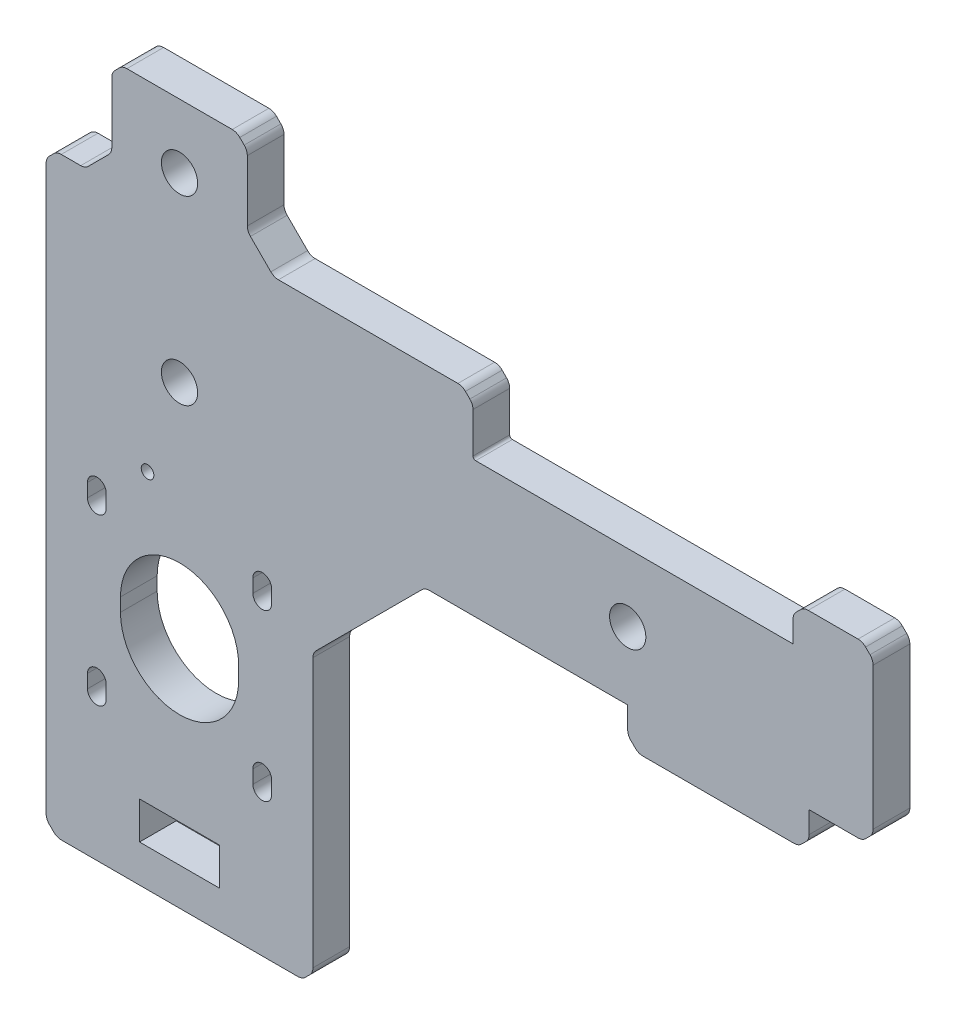
SolidWorks part; units mm, degrees
ref_plane "Front Plane" through (0, 0, 0) normal (0, 0, 1) x (1, 0, 0)
ref_plane "Top Plane" through (0, 0, 0) normal (0, 1, 0) x (1, 0, 0)
ref_plane "Right Plane" through (0, 0, 0) normal (1, 0, 0) x (0, 0, -1)
sketch "Sketch1" plane through (0, 0, 0) normal (0, 0, 1) x (1, 0, 0)
  line L1 (25, -65.675) -> (-25, -65.675)
  line L2 (25, -65.675) -> (25, 65.675)
  line L3 (25, 65.675) -> (-25, 65.675)
  line L4 (-25, -65.675) -> (-25, 65.675)
  line L5 (25, -65.675) -> (-25, 65.675) construction
  line L6 (25, 65.675) -> (-25, -65.675) construction
  point P0 (0, 0)
  dimension "D1" = 50
  dimension "D2" = 131.35
extrude "Boss-Extrude1" add sketch "Sketch1" along normal blind 6.88
sketch "Sketch2" plane through (0, 0, 6.88) normal (0, 0, 1) x (1, 0, 0)
  line L1 (15.5, -36.175) -> (-15.5, -36.175) construction
  line L2 (15.5, -36.175) -> (15.5, -5.175) construction
  line L3 (15.5, -5.175) -> (-15.5, -5.175) construction
  line L4 (-15.5, -36.175) -> (-15.5, -5.175) construction
  line L5 (15.5, -36.175) -> (-15.5, -5.175) construction
  line L6 (15.5, -5.175) -> (-15.5, -36.175) construction
  line L7 (-25, -65.675) -> (25, -65.675) construction
  line L8 (25, 65.675) -> (-25, 65.675) construction
  circle A0 centre (0, -20.675) radius 11.075
  circle A1 centre (-15.5, -5.175) radius 1.75
  circle A2 centre (-15.5, -36.175) radius 1.75
  circle A3 centre (15.5, -36.175) radius 1.75
  circle A4 centre (15.5, -5.175) radius 1.75
  circle A5 centre (0, 53.675) radius 3.4
  circle A6 centre (0, 19.675) radius 3.4
  dimension "D3" = 3.5
  dimension "D4" = 22.15
  dimension "D7" = 6.8
  dimension "D1" = 31
  dimension "D2" = 45
  dimension "D5" = 34
  dimension "D6" = 12
extrude "Cut-Extrude1" cut sketch "Sketch2" against normal through all
sketch "Sketch3" plane through (0, 0, 6.88) normal (0, 0, 1) x (1, 0, 0)
  line L0 (-25, -65.675) -> (25, -65.675) construction
  line L1 (7.5, -51.675) -> (-7.5, -51.675)
  line L2 (7.5, -51.675) -> (7.5, -58.675)
  line L3 (7.5, -58.675) -> (-7.5, -58.675)
  line L4 (-7.5, -51.675) -> (-7.5, -58.675)
  line L5 (7.5, -51.675) -> (-7.5, -58.675) construction
  line L6 (7.5, -58.675) -> (-7.5, -51.675) construction
  point P0 (0, -55.175)
  dimension "D1" = 15
  dimension "D2" = 7
  dimension "D3" = 7
extrude "Cut-Extrude2" cut sketch "Sketch3" against normal blind 6.88
sketch "Sketch4" plane through (0, 0, 6.88) normal (0, 0, 1) x (1, 0, 0)
  line L0 (25, 9.325) -> (130, 9.325)
  line L1 (25, -65.675) -> (25, 65.675) construction
  line L2 (130, 9.325) -> (130, 34.725)
  line L3 (130, 34.725) -> (25, 34.725)
  line L4 (25, 34.725) -> (25, 9.325)
  line L5 (-25, 65.675) -> (-25, -65.675) construction
  line L6 (130, 22.025) -> (0, 22.025) construction
  line L7 (-25, -65.675) -> (25, -65.675) construction
  dimension "D1" = 25.4
  dimension "D2" = 155
  dimension "D3" = 75
extrude "Boss-Extrude2" add sketch "Sketch4" against normal up to vertex (6.88 mm away) up to point (25, 65.675, 0)
sketch "Sketch5" plane through (0, 0, 6.88) normal (0, 0, 1) x (1, 0, 0)
  line L0 (118, 22.025) -> (84, 22.025) construction
  line L1 (84, 22.025) -> (0, 22.025) construction
  line L2 (130, 9.325) -> (130, 34.725) construction
  circle A0 centre (118, 22.025) radius 3.4
  circle A1 centre (84, 22.025) radius 3.4
  point P8 (130, 22.025)
  dimension "D3" = 6.8
  dimension "D1" = 12
  dimension "D2" = 34
extrude "Cut-Extrude3" cut sketch "Sketch5" against normal blind 6.88
sketch "Sketch6" plane through (0, 0, 6.88) normal (0, 0, 1) x (1, 0, 0)
  line L0 (25, 9.325) -> (130, 9.325) construction
  line L1 (84, 9.325) -> (118, 9.325)
  line L2 (84, 9.325) -> (84, 2.445)
  line L3 (84, 2.445) -> (118, 2.445)
  line L4 (118, 9.325) -> (118, 2.445)
  line L5 (84, 34.725) -> (84, 9.325) construction
  line L6 (118, 22.025) -> (118, 9.325) construction
  line L7 (130, 34.725) -> (25, 34.725) construction
  line L8 (130, 34.725) -> (115, 34.725)
  line L9 (130, 34.725) -> (130, 41.605)
  line L10 (130, 41.605) -> (115, 41.605)
  line L11 (115, 34.725) -> (115, 41.605)
  dimension "D1" = 6.88
  dimension "D2" = 15
  dimension "D3" = 34
extrude "Boss-Extrude3" add sketch "Sketch6" against normal up to vertex (6.88 mm away) up to point (130, 34.725, 0)
sketch "Sketch7" plane through (0, 0, 6.88) normal (0, 0, 1) x (1, 0, 0)
  line L0 (-25, 65.675) -> (-25, -65.675) construction
  line L5 (115, 34.725) -> (25, 34.725) construction
  line L8 (-25, 65.675) -> (-12.7, 65.675)
  line L9 (-25, 65.675) -> (-25, 45.605)
  line L10 (-25, 45.605) -> (-12.7, 45.605)
  line L11 (-12.7, 65.675) -> (-12.7, 45.605)
  line L12 (25, 65.675) -> (12.7, 65.675)
  line L13 (25, 65.675) -> (25, 45.605)
  line L14 (25, 45.605) -> (12.7, 45.605)
  line L15 (12.7, 65.675) -> (12.7, 45.605)
  dimension "D1" = 25.4
  dimension "D2" = 10.88
extrude "Cut-Extrude4" cut sketch "Sketch7" against normal blind 6.88
sketch "Sketch8" plane through (0, 0, 6.88) normal (0, 0, 1) x (1, 0, 0)
  line L0 (-6, 2.175) -> (6, 2.175) construction
  line L1 (12.7, 65.675) -> (-12.7, 65.675) construction
  line L2 (130, 9.325) -> (130, 41.605) construction
  line L3 (41.1, 28.025) -> (41.1, 16.025) construction
  line L4 (41.1, 22.025) -> (118, 22.025) construction
  circle A0 centre (-6, 2.175) radius 1.1811
  circle A1 centre (6, 2.175) radius 1.1811 construction
  circle A2 centre (41.1, 28.025) radius 1.1811 construction
  circle A3 centre (41.1, 16.025) radius 1.1811 construction
  point P4 (0, 2.175)
  dimension "D1" = 2.3622
  dimension "D2" = 12
  dimension "D3" = 63.5
  dimension "D4" = 12
  dimension "D5" = 88.9
extrude "Cut-Extrude5" cut sketch "Sketch8" against normal blind 6.88
sketch "Sketch9" plane through (0, 0, 6.88) normal (0, 0, 1) x (1, 0, 0)
  circle A0 centre (15.5, -36.175) radius 3
  circle A1 centre (-15.5, -36.175) radius 3
  circle A2 centre (-15.5, -5.175) radius 3
  circle A4 centre (15.5, -5.175) radius 3
  dimension "D1" = 6
extrude "Cut-Extrude6" [suppressed] cut sketch "Sketch9" against normal blind 6.88
sketch "Sketch10" plane through (0, 0, 6.88) normal (0, 0, 1) x (1, 0, 0)
  circle A0 centre (0, -20.675) radius 13
  dimension "D1" = 26
extrude "Boss-Extrude4" [suppressed] add sketch "Sketch10" against normal up to vertex up to point (-25, -65.675, 0)
sketch "Sketch11" plane through (0, 0, 6.88) normal (0, 0, 1) x (1, 0, 0)
  line L0 (115, 34.725) -> (25, 34.725) construction
  line L1 (25, 45.605) -> (55, 45.605)
  line L2 (25, 45.605) -> (25, 34.725)
  line L3 (25, 34.725) -> (55, 34.725)
  line L4 (55, 45.605) -> (55, 34.725)
  dimension "D1" = 30
extrude "Boss-Extrude5" add sketch "Sketch11" against normal up to vertex (6.88 mm away) up to point (12.7, 45.605, 0)
chamfer "Chamfer2" distance 21 angle 45 1 edges at (25, 9.325, 3.44)
sketch "Sketch12" plane through (0, 0, 6.88) normal (0, 0, 1) x (1, 0, 0)
  line L0 (-15.5, -5.175) -> (-15.5, -7.675) construction
  line L1 (-13.75, -5.175) -> (-13.75, -7.675)
  line L2 (-17.25, -5.175) -> (-17.25, -7.675)
  line L3 (15.5, -5.175) -> (15.5, -7.675) construction
  line L4 (17.25, -5.175) -> (17.25, -7.675)
  line L5 (13.75, -5.175) -> (13.75, -7.675)
  line L6 (-15.5, -36.175) -> (-15.5, -38.675) construction
  line L7 (-13.75, -36.175) -> (-13.75, -38.675)
  line L8 (-17.25, -36.175) -> (-17.25, -38.675)
  line L9 (15.5, -36.175) -> (15.5, -38.675) construction
  line L10 (17.25, -36.175) -> (17.25, -38.675)
  line L11 (13.75, -36.175) -> (13.75, -38.675)
  line L12 (0, -20.675) -> (0, -23.175) construction
  line L13 (11.075, -20.675) -> (11.075, -23.175)
  line L14 (-11.075, -20.675) -> (-11.075, -23.175)
  arc A0 (-13.75, -5.175) -> (-17.25, -5.175) centre (-15.5, -5.175) ccw
  arc A1 (-17.25, -7.675) -> (-13.75, -7.675) centre (-15.5, -7.675) ccw
  circle A2 centre (-15.5, -5.175) radius 1.75 construction
  arc A3 (17.25, -5.175) -> (13.75, -5.175) centre (15.5, -5.175) ccw
  arc A4 (13.75, -7.675) -> (17.25, -7.675) centre (15.5, -7.675) ccw
  arc A5 (-13.75, -36.175) -> (-17.25, -36.175) centre (-15.5, -36.175) ccw
  arc A6 (-17.25, -38.675) -> (-13.75, -38.675) centre (-15.5, -38.675) ccw
  arc A7 (17.25, -36.175) -> (13.75, -36.175) centre (15.5, -36.175) ccw
  arc A8 (13.75, -38.675) -> (17.25, -38.675) centre (15.5, -38.675) ccw
  arc A9 (11.075, -20.675) -> (-11.075, -20.675) centre (0, -20.675) ccw
  arc A10 (-11.075, -23.175) -> (11.075, -23.175) centre (0, -23.175) ccw
  circle A11 centre (0, -20.675) radius 11.075 construction
  point P3 (-15.5, -6.425)
  point P12 (15.5, -6.425)
  point P19 (-15.5, -37.425)
  point P26 (15.5, -37.425)
  point P35 (0, -21.925)
  dimension "D1" = 2.5
  dimension "D2" = 2.5
extrude "Cut-Extrude7" cut sketch "Sketch12" against normal blind 10
sketch "Sketch13" [suppressed] plane through (0, 0, 6.88) normal (0, 0, 1) x (1, 0, 0)
  line L0 (-15.5, -5.175) -> (-15.5, -7.675) construction
  line L1 (-12.5, -5.175) -> (-12.5, -7.675)
  line L2 (-18.5, -5.175) -> (-18.5, -7.675)
  line L3 (15.5, -5.175) -> (15.5, -7.675) construction
  line L4 (18.5, -5.175) -> (18.5, -7.675)
  line L5 (12.5, -5.175) -> (12.5, -7.675)
  line L6 (15.5, -36.175) -> (15.5, -38.675) construction
  line L7 (18.5, -36.175) -> (18.5, -38.675)
  line L8 (12.5, -36.175) -> (12.5, -38.675)
  line L9 (-15.5, -36.175) -> (-15.5, -38.675) construction
  line L10 (-12.5, -36.175) -> (-12.5, -38.675)
  line L11 (-18.5, -36.175) -> (-18.5, -38.675)
  arc A0 (-12.5, -5.175) -> (-18.5, -5.175) centre (-15.5, -5.175) ccw
  arc A1 (-18.5, -7.675) -> (-12.5, -7.675) centre (-15.5, -7.675) ccw
  circle A2 centre (-15.5, -5.175) radius 3 construction
  arc A3 (18.5, -5.175) -> (12.5, -5.175) centre (15.5, -5.175) ccw
  arc A4 (12.5, -7.675) -> (18.5, -7.675) centre (15.5, -7.675) ccw
  arc A5 (18.5, -36.175) -> (12.5, -36.175) centre (15.5, -36.175) ccw
  arc A6 (12.5, -38.675) -> (18.5, -38.675) centre (15.5, -38.675) ccw
  arc A7 (-12.5, -36.175) -> (-18.5, -36.175) centre (-15.5, -36.175) ccw
  arc A8 (-18.5, -38.675) -> (-12.5, -38.675) centre (-15.5, -38.675) ccw
  point P3 (-15.5, -6.425)
  point P12 (15.5, -6.425)
  point P19 (15.5, -37.425)
  point P26 (-15.5, -37.425)
  dimension "D1" = 2.5
extrude "Cut-Extrude8" [suppressed] cut sketch "Sketch13" against normal blind 10
sketch "Sketch14" [suppressed] plane through (0, 0, 6.88) normal (0, 0, 1) x (1, 0, 0)
  line L0 (2.5, -7) -> (-2.5, -7) construction
  line L1 (2.5, -9) -> (-2.5, -9)
  line L2 (2.5, -5) -> (-2.5, -5)
  arc A0 (2.5, -9) -> (2.5, -5) centre (2.5, -7) ccw
  arc A1 (-2.5, -5) -> (-2.5, -9) centre (-2.5, -7) ccw
  point P2 (0, -7)
  dimension "D1" = 4
  dimension "D2" = 5
  dimension "D3" = 7
extrude "Cut-Extrude9" [suppressed] cut sketch "Sketch14" against normal through all
chamfer "Chamfer5" distance 5 angle 45 2 edges at (-12.7, 45.605, 3.44) (12.7, 45.605, 3.44)
chamfer "Chamfer3" distance 2 angle 45 11 edges at (-25, -65.675, 3.44) (84, 2.445, 3.44) (118, 2.445, 3.44) (130, 9.325, 3.44) (115, 41.605, 3.44) (130, 41.605, 3.44) (-25, 45.605, 3.44) (-12.7, 65.675, 3.44) (12.7, 65.675, 3.44) (55, 45.605, 3.44) (25, -65.675, 3.44)
sketch "Sketch15" [suppressed] plane through (0, 0, 6.88) normal (0, 0, 1) x (1, 0, 0)
  circle A0 centre (84, 22.025) radius 7.2715
extrude "Boss-Extrude6" [suppressed] add sketch "Sketch15" against normal up to vertex up to point (55, 34.725, 0)
sketch "Sketch16" plane through (0, 0, 6.88) normal (0, 0, 1) x (1, 0, 0)
  circle A0 centre (118, 22.025) radius 7.069
extrude "Boss-Extrude7" add sketch "Sketch16" against normal up to vertex (6.88 mm away) up to point (55, 34.725, 0)
fillet "Fillet1" [suppressed] radius 2
fillet "Fillet2" radius 2 28 edges at (17.7, 45.605, 3.44) (12.7, 50.605, 3.44) (12.7, 63.675, 3.44) (10.7, 65.675, 3.44) (-10.7, 65.675, 3.44) (-12.7, 63.675, 3.44) (-12.7, 50.605, 3.44) (-17.7, 45.605, 3.44) (-25, 43.605, 3.44) (-25, -63.675, 3.44) (-23, -65.675, 3.44) (23, -65.675, 3.44) (25, -63.675, 3.44) (25, -11.675, 3.44) (46, 9.325, 3.44) (84, 4.445, 3.44) (86, 2.445, 3.44) (116, 2.445, 3.44) (118, 4.445, 3.44) (128, 9.325, 3.44) (130, 11.325, 3.44) (130, 39.605, 3.44) (128, 41.605, 3.44) (117, 41.605, 3.44) (115, 39.605, 3.44) (55, 43.605, 3.44) (53, 45.605, 3.44) (-23, 45.605, 3.44)
fillet "Fillet3" [suppressed] radius 0.5
fillet "Fillet4" radius 0.5 1 edges at (55, 34.725, 3.44)
